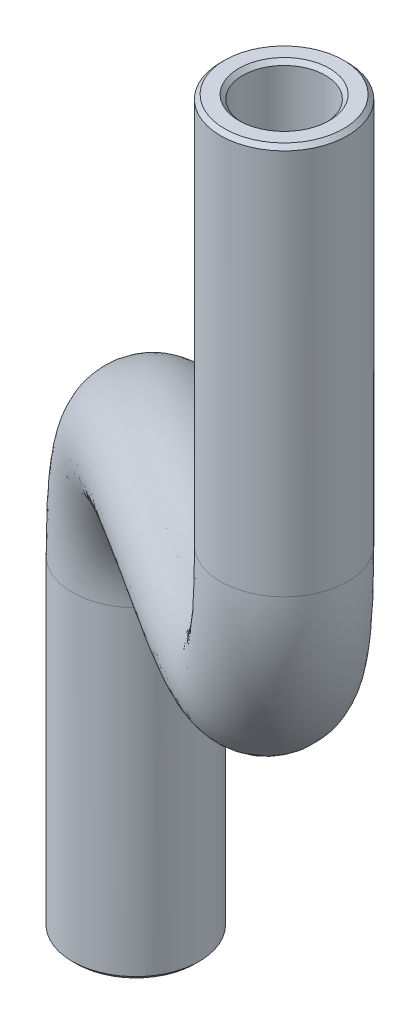
SolidWorks part; units mm, degrees
ref_plane "Front Plane" through (0, 0, 0) normal (0, 0, 1) x (1, 0, 0)
ref_plane "Top Plane" through (0, 0, 0) normal (0, 1, 0) x (1, 0, 0)
ref_plane "Right Plane" through (0, 0, 0) normal (1, 0, 0) x (0, 0, -1)
sketch3d "3DSketch1"
  line L0 (114.825, -74.325, 25.85) -> (114.825, -62.025, 25.85)
  line L1 (93.825, -103.4823, 9.525) -> (93.825, -93.2823, 9.525)
  spline S0 degree 3 poles (93.825, -93.2823, 9.525) (93.825, -87.9754, 9.525) (104.325, -83.8809, 17.6875) (114.825, -80.0317, 25.85) (114.825, -74.325, 25.85) knots 0 0 0 0 0.487413 1 1 1 1
sketch "Sketch1" plane through (0, -95.7823, 0) normal (0, 1, 0) x (1, 0, 0)
  circle A0 centre (93.825, -9.525) radius 1.3
  circle A1 centre (93.825, -9.525) radius 2
  circle A2 centre (93.825, -9.525) radius 3.5 construction
  dimension "D1" = 2.6
  dimension "D2" = 4
sweep "Sweep1" add profiles "Sketch1" path "3DSketch1"
chamfer "Chamfer1" distance 0.127 angle 45 4 edges at (91.825, -103.4823, 9.525) (92.525, -103.4823, 9.525) (112.825, -62.025, 25.85) (113.525, -62.025, 25.85)
